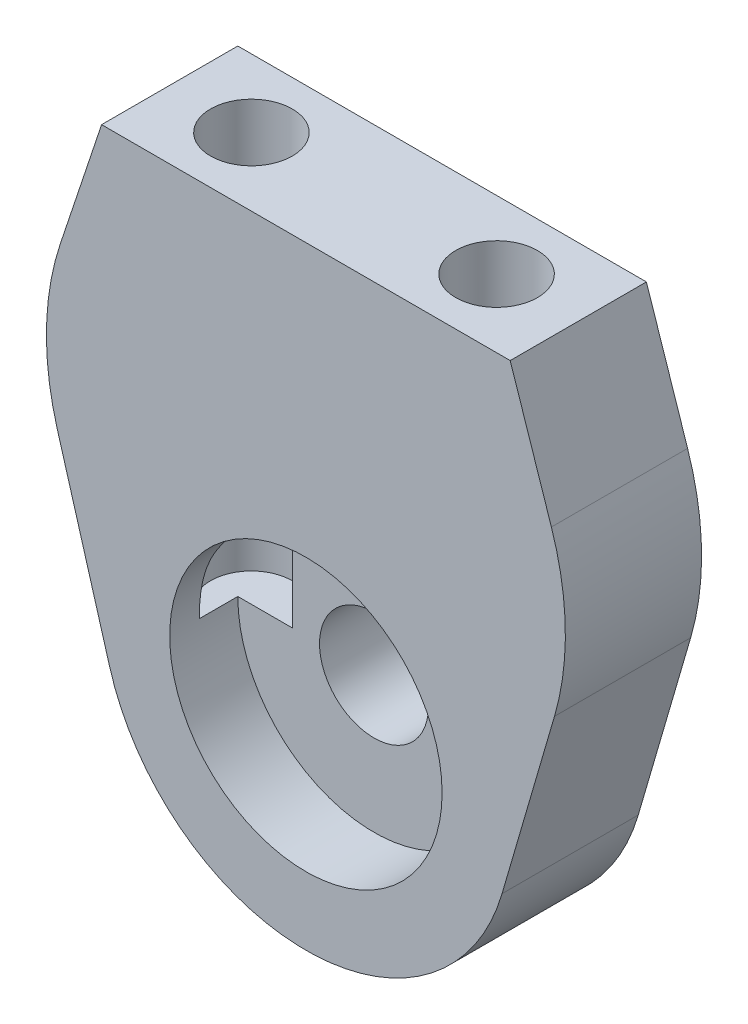
SolidWorks part; units mm, degrees
material "A2017"
ref_plane "正面" through (0, 0, 0) normal (0, 0, 1) x (1, 0, 0)
ref_plane "平面" through (0, 0, 0) normal (0, 1, 0) x (1, 0, 0)
ref_plane "右側面" through (0, 0, 0) normal (1, 0, 0) x (0, 0, -1)
sketch "ｽｹｯﾁ1" plane through (0, 0, 0) normal (0, 0, 1) x (1, 0, 0)
  circle A0 centre (0, 0) radius 7.5
  circle A1 centre (0, 0) radius 2
  dimension "D1" = 4
  dimension "D2" = 15
extrude "ﾎﾞｽ - 押し出し1" add sketch "ｽｹｯﾁ1" along normal blind 5
sketch "ｽｹｯﾁ2" plane through (0, 0, 5) normal (0, 0, 1) x (1, 0, 0)
  line L0 (0, 0) -> (0, 15) construction
  line L1 (-7.5, 0) -> (-7.5, 15)
  line L2 (-7.5, 15) -> (7.5, 15)
  line L3 (7.5, 15) -> (7.5, 0)
  circle A0 centre (0, 0) radius 7.5 construction
  arc A1 (-7.5, 0) -> (7.5, 0) centre (0, 0) cw
  dimension "D1" = 15
extrude "ﾎﾞｽ - 押し出し2" add sketch "ｽｹｯﾁ2" against normal up to surface (5 mm away) up to face at (7.5, 0, 0)
sketch "ｽｹｯﾁ3" plane through (0, 15, 0) normal (0, 1, 0) x (1, 0, 0)
  line L0 (-7.5, -2.5) -> (7.5, -2.5) construction
  line L3 (-7.5, 0) -> (-7.5, -5) construction
  line L4 (7.5, 0) -> (7.5, -5) construction
  line L5 (0, 0) -> (0, -5) construction
  line L6 (-7.5, 0) -> (7.5, 0) construction
  line L7 (7.5, -5) -> (-7.5, -5) construction
  circle A0 centre (-4.5, -2.5) radius 1.5
  circle A1 centre (4.5, -2.5) radius 1.5
  dimension "D1" = 3
  dimension "D2" = 3
extrude "ｶｯﾄ - 押し出し1" cut sketch "ｽｹｯﾁ3" against normal blind 15
sketch "ｽｹｯﾁ4" plane through (0, 0, 5) normal (0, 0, 1) x (1, 0, 0)
  line L0 (0, 0) -> (0, 15) construction
  line L1 (7.5, 15) -> (-7.5, 15) construction
  line L2 (0, 7.5) -> (-10, 7.5) construction
  line L3 (-10, 7.5) -> (-7.5, 15) construction
  line L4 (-10, 7.5) -> (-7.2, -2.1) construction
  line L5 (-7.5, 15) -> (-10, 7.5)
  line L6 (-10, 7.5) -> (-7.2, -2.1)
  line L7 (-7.5, 0) -> (-7.5, 15)
  line L8 (10, 7.5) -> (7.2, -2.1) construction
  line L9 (10, 7.5) -> (7.5, 15) construction
  line L10 (7.5, 0) -> (7.5, 15)
  line L11 (10, 7.5) -> (7.2, -2.1)
  line L12 (7.5, 15) -> (10, 7.5)
  arc A0 (-7.5, 0) -> (7.5, 0) centre (0, 0) ccw construction
  arc A1 (-7.2, -2.1) -> (-7.5, 0) centre (0, 0) cw
  arc A2 (7.2, -2.1) -> (7.5, 0) centre (0, 0) ccw
  dimension "D1" = 10
extrude "ﾎﾞｽ - 押し出し3" add sketch "ｽｹｯﾁ4" against normal up to surface (5 mm away) up to face at (0, 5.625, 0)
fillet "ﾌｨﾚｯﾄ1" radius 10 2 edges at (10, 7.5, 2.5) (-10, 7.5, 2.5)
sketch "ｽｹｯﾁ5" plane through (0, 0, 5) normal (0, 0, 1) x (1, 0, 0)
  line L0 (0, 0) -> (0, 12) construction
  line L1 (0, 12) -> (-8.1875, 12) construction
  line L2 (-9.1253, 4.5012) -> (-7.2, -2.1) construction
  line L3 (-8.1875, 15) -> (8.1875, 15)
  line L4 (9.0122, 10.4635) -> (7.5, 15) construction
  line L5 (7.5, 15) -> (-7.5, 15) construction
  line L6 (-7.5, 15) -> (-9.0122, 10.4635) construction
  line L7 (9.0122, 10.4635) -> (7.5, 15)
  line L8 (7.5, 15) -> (-7.5, 15)
  line L9 (-7.5, 15) -> (-9.0122, 10.4635)
  arc A0 (-8.1875, 15) -> (-6.4921, 14.475) centre (-8.1875, 12) ccw
  arc A1 (8.1875, 15) -> (6.4921, 14.475) centre (8.1875, 12) cw
  arc A2 (9.1253, 4.5012) -> (9.0122, 10.4635) centre (-0.4747, 7.3012) ccw construction
  arc A3 (-9.0122, 10.4635) -> (-9.1253, 4.5012) centre (0.4747, 7.3012) ccw construction
  arc A4 (6.4921, 14.475) -> (9.0122, 10.4635) centre (-0.4747, 7.3012) ccw
  arc A5 (-9.0122, 10.4635) -> (-6.4921, 14.475) centre (0.4747, 7.3012) ccw
  dimension "D2" = 6
  dimension "D1" = 12
extrude "ｶｯﾄ - 押し出し2" [suppressed] cut sketch "ｽｹｯﾁ5" against normal through all
sketch "ｽｹｯﾁ6" [suppressed] plane through (0, 0, 5) normal (0, 0, 1) x (1, 0, 0)
  arc A0 (9.8123, 12.4863) -> (6.852, 15) centre (6.852, 12) ccw construction
  arc A1 (-6.852, 15) -> (-9.8123, 12.4863) centre (-6.852, 12) ccw construction
  circle A2 centre (6.852, 12) radius 3
  circle A3 centre (-6.852, 12) radius 3
extrude "ﾎﾞｽ - 押し出し4" [suppressed] add sketch "ｽｹｯﾁ6" against normal up to surface (5 mm away) up to face at (0, 6.2933, 0)
sketch "ｽｹｯﾁ7" [suppressed] plane through (0, 0, 5) normal (0, 0, 1) x (1, 0, 0)
  circle A0 centre (6.852, 12) radius 1.5
  circle A1 centre (-6.852, 12) radius 1.5
  dimension "D1" = 3
  dimension "D2" = 3
extrude "ｶｯﾄ - 押し出し3" [suppressed] cut sketch "ｽｹｯﾁ7" against normal through all
sketch "ｽｹｯﾁ8" [suppressed] plane through (0, 0, 5) normal (0, 0, 1) x (1, 0, 0)
  line L0 (-6.852, 15) -> (-9.852, 15)
  line L1 (-9.852, 15) -> (-9.852, 11.7185)
  line L2 (-9.852, 11.7185) -> (-9.7997, 11.4419)
  line L3 (0, 0) -> (0, 15) construction
  line L4 (-6.852, 15) -> (6.852, 15) construction
  line L5 (9.852, 11.7185) -> (9.7997, 11.4419)
  line L6 (9.852, 15) -> (9.852, 11.7185)
  line L7 (6.852, 15) -> (9.852, 15)
  arc A0 (-7.3691, -1.3953) -> (7.3691, -1.3953) centre (0, 0) ccw construction
  arc A1 (-6.852, 15) -> (-9.7269, 11.1426) centre (-6.852, 12) ccw construction
  arc A2 (-6.852, 15) -> (-9.7997, 11.4419) centre (-6.852, 12) ccw
  arc A3 (6.852, 15) -> (9.7997, 11.4419) centre (6.852, 12) cw
extrude "ﾎﾞｽ - 押し出し5" [suppressed] add sketch "ｽｹｯﾁ8" against normal up to surface (5 mm away) up to face at (0, 6.2933, 0)
sketch "ｽｹｯﾁ10" [suppressed] plane through (0, 0, 0) normal (0, 0, -1) x (-1, 0, 0)
  line L0 (0, 15) -> (0, 0) construction
  line L1 (9.852, 15) -> (-9.852, 15) construction
sketch "ｽｹｯﾁ11" plane through (0, 0, 5) normal (0, 0, 1) x (1, 0, 0)
  circle A0 centre (0, 0) radius 5
  dimension "D1" = 10
extrude "ｶｯﾄ - 押し出し4" cut sketch "ｽｹｯﾁ11" against normal blind 2.5
